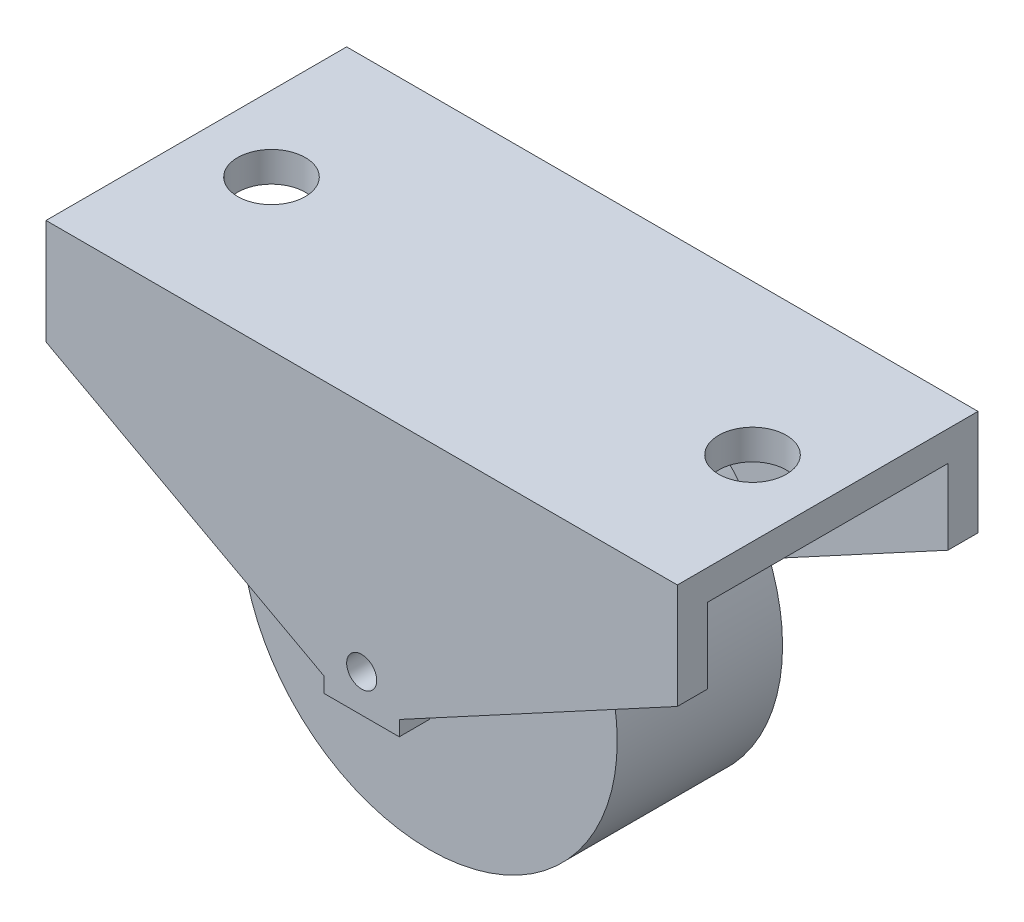
SolidWorks part; units mm, degrees
ref_plane "Спереди" through (0, 0, 0) normal (0, 0, 1) x (1, 0, 0)
ref_plane "Сверху" through (0, 0, 0) normal (0, 1, 0) x (1, 0, 0)
ref_plane "Справа" through (0, 0, 0) normal (1, 0, 0) x (0, 0, -1)
sketch "Эскиз1" plane through (0, 0, 0) normal (0, 1, 0) x (1, 0, 0)
  line L1 (-21, -10) -> (21, -10)
  line L2 (-21, -10) -> (-21, 10)
  line L3 (-21, 10) -> (21, 10)
  line L5 (-21, -10) -> (21, 10) construction
  line L6 (-21, 10) -> (21, -10) construction
  line L9 (-16, 0) -> (16, 0) construction
  line L10 (21, -10) -> (21, 10)
  circle A4 centre (-16, 0) radius 2.25
  circle A5 centre (16, 0) radius 2.25
  point P0 (0, 0)
  point P10 (0, 0)
  point P11 (0, 0)
  point P15 (0, 0)
  dimension "D3" = 4.5
  dimension "D4" = 4.5
  dimension "D5" = 32
  dimension "D1" = 42
  dimension "D2" = 20
extrude "Бобышка-Вытянуть1" add sketch "Эскиз1" along normal blind 2
sketch "Эскиз2" plane through (0, 0, 0) normal (0, 0, 1) x (1, 0, 0)
  line L2 (-46.046, -26) -> (131.9496, -26) construction
  line L3 (-21, 2) -> (21, 2) construction
  circle A0 centre (0, -13.5) radius 12.5
  dimension "D1" = 25
  dimension "D3" = 28
extrude "Бобышка-Вытянуть2" add sketch "Эскиз2" along normal blind 11 from offset 5.5 separate body offset against normal yes
sketch "Эскиз3" plane through (0, 0, 10) normal (0, 0, 1) x (1, 0, 0)
  line L2 (-21, -5) -> (-2.5, -15)
  line L5 (-21, 0) -> (21, 0)
  line L6 (21, 0) -> (21, -5)
  line L7 (-21, 0) -> (-21, -5)
  line L8 (-12.0225, -10.078) -> (12.0225, -16.922) construction
  line L9 (-2.5, -16) -> (2.5, -16)
  line L10 (2.5, -16) -> (2.5, -15)
  line L11 (-2.5, -16) -> (-2.5, -15)
  line L12 (2.5, -15) -> (21, -5)
  circle A1 centre (0, -13.5) radius 12.5 construction
  point P8 (0, -13.5)
  point P9 (0, 0)
  point P10 (0, -13.5)
  point P12 (-2.5, -15)
  point P16 (-21, -2.7137)
  dimension "D1" = 2.5
  dimension "D2" = 2.5
  dimension "D3" = 2.5
  dimension "D4" = 1
  dimension "D5" = 5
extrude "Бобышка-Вытянуть3" add sketch "Эскиз3" against normal blind 2
pattern_linear "Линейный массив1" count 2 spacing 18 along (0, 0, -1) of "Бобышка-Вытянуть3"
sketch "Эскиз4" plane through (0, 0, -8) normal (0, 0, 1) x (1, 0, 0)
  circle A0 centre (0, -13.5) radius 1
  dimension "D1" = 2
extrude "Вырез-Вытянуть1" cut sketch "Эскиз4" against normal through all both and the other way through all
